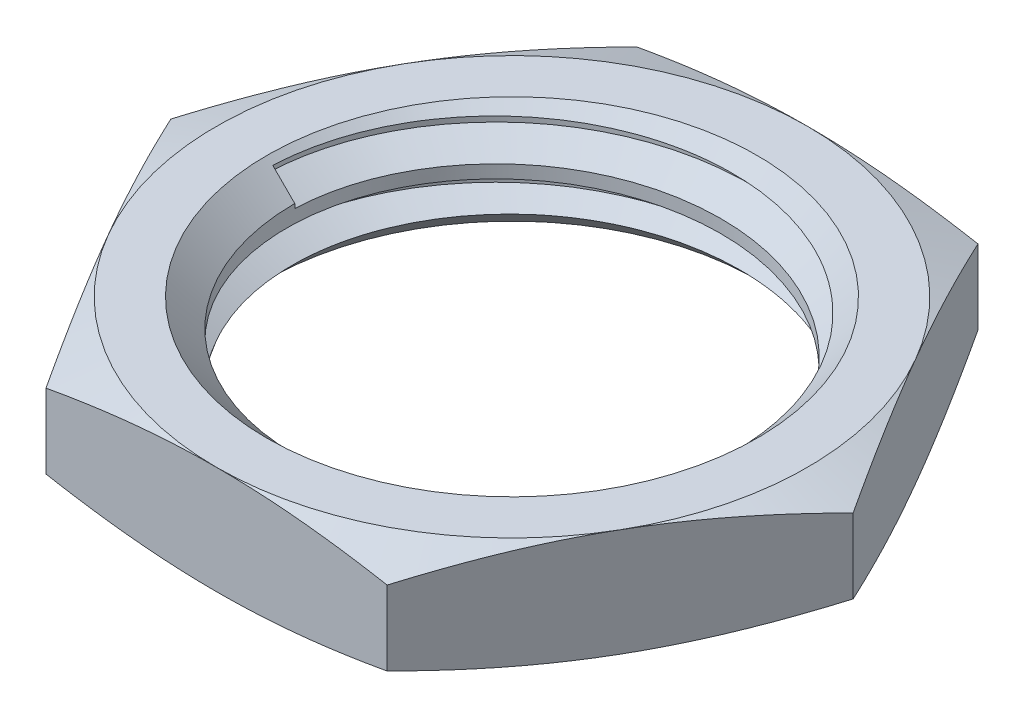
SolidWorks part; units mm, degrees
material "1023 Carbon Steel Sheet (SS)"
ref_plane "Front Plane" through (0, 0, 0) normal (0, 0, 1) x (1, 0, 0)
ref_plane "Top Plane" through (0, 0, 0) normal (0, 1, 0) x (1, 0, 0)
ref_plane "Right Plane" through (0, 0, 0) normal (1, 0, 0) x (0, 0, -1)
sketch "Sketch1" plane through (0, 0, 0) normal (0, 1, 0) x (1, 0, 0)
  line L1 (9.815, 0) -> (4.9075, 8.5)
  line L2 (4.9075, 8.5) -> (-4.9075, 8.5)
  line L3 (-4.9075, 8.5) -> (-9.815, 0)
  line L4 (-9.815, 0) -> (-4.9075, -8.5)
  line L5 (-4.9075, -8.5) -> (4.9075, -8.5)
  line L6 (4.9075, -8.5) -> (9.815, 0)
  circle A0 centre (0, 0) radius 8.5 construction
  dimension "D1" = 17
extrude "Boss-Extrude1" add sketch "Sketch1" along normal blind 3.1
sketch "Sketch2" plane through (0, 3.1, 0) normal (0, 1, 0) x (1, 0, 0)
  circle A0 centre (0, 0) radius 8.5
extrude "Cut-Extrude1" cut sketch "Sketch2" against normal blind 3.1 draft 70 flip side to cut
sketch "Sketch3" plane through (0, 0, 0) normal (0, -1, 0) x (1, 0, 0)
  circle A0 centre (0, 0) radius 8.5
extrude "Cut-Extrude2" cut sketch "Sketch3" against normal blind 3.1 draft 70 flip side to cut
sketch "Sketch6" plane through (0, 3.1, 0) normal (0, 1, 0) x (1, 0, 0)
  point P0 (0, 0)
hole_wizard "Tap Drill for M14x1.5 Tap1" positions "Sketch6" profile "Sketch5" hole size "M14x1.5" standard "ANSI Metric"
sketch "Sketch5" plane through (0, 3.1, 0) normal (1, 0, 0) x (0, 0, 1)
  line L0 (0, 0) -> (0, 10.6554)
  line L1 (0, 10.6554) -> (6.25, 6.9)
  line L2 (6.25, 6.9) -> (6.25, 0)
  line L5 (6.25, 0) -> (0, 0)
  line L10 (0, 10.6554) -> (-6.25, 6.9) construction
  line L11 (0, -6.35) -> (0, 107.95) construction
  dimension "Hole Dia." = 12.5
  dimension "Hole Depth" = 6.9
  dimension "Drill Angle" = 118
chamfer "Chamfer1" distance 0.8 angle 45 1 edges at (0, 3.1, 6.25)
chamfer "Chamfer2" distance 0.8 angle 45 1 edges at (0, 0, 6.25)
thread "Thread1" pitch 1.5 start angle 0, offset 1, length 0, pitch 1.5, diameter 12.5
ref_plane "Plane1" through (-6.25, 3.3, 0) normal (0, 0, 1) x (-1, 0, 0)
sketch "Thread Profile1" plane through (-6.25, 3.3, 0) normal (0, 0, 1) x (-1, 0, 0)
  line L0 (0, 0) -> (0, 1.5) construction
  line L1 (0, 0) -> (0.8119, 0.4687)
  line L2 (0.8119, 0.4687) -> (0.8119, 0.6562)
  line L3 (0.8119, 0.6562) -> (0, 1.125)
  line L4 (0.8119, 0.5625) -> (0, 0.5625) construction
  line L11 (0, 0) -> (0, 1.125)
  point P2 (0, 0)
  dimension "Pitch" = 1.5
  dimension "Profile_Angle" = 60
  dimension "Profile_Land" = 0.1875
  dimension "Profile_Height" = 0.8119
